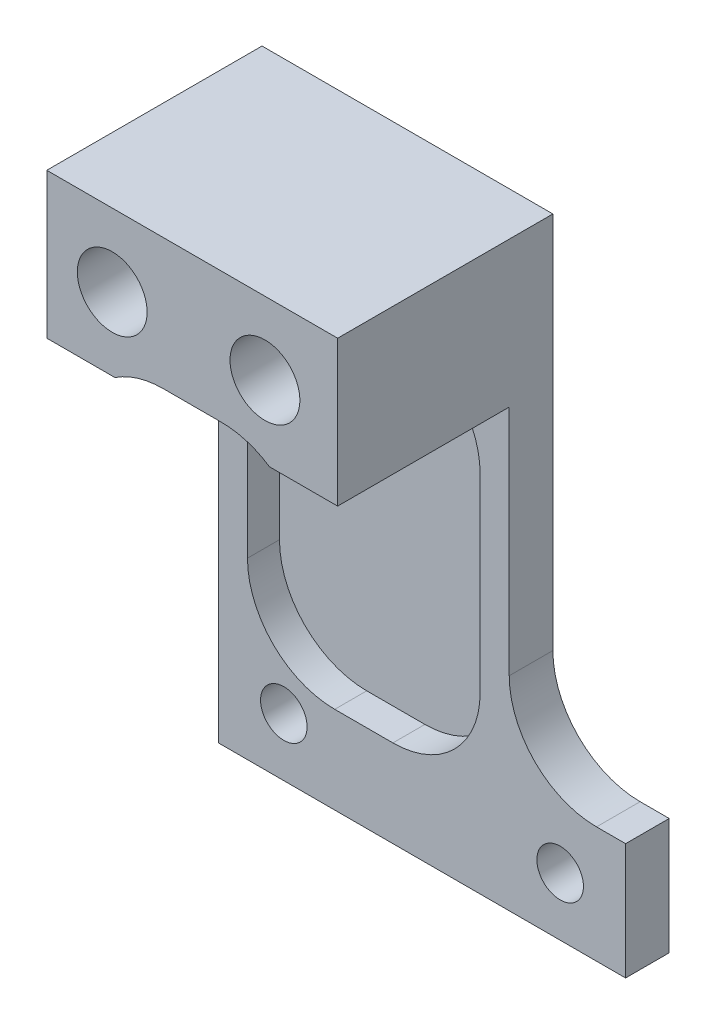
SolidWorks part; units mm, degrees
material "6061-T6 (SS)"
ref_plane "Front Plane" through (0, 0, 0) normal (0, 0, 1) x (1, 0, 0)
ref_plane "Top Plane" through (0, 0, 0) normal (0, 1, 0) x (1, 0, 0)
ref_plane "Right Plane" through (0, 0, 0) normal (1, 0, 0) x (0, 0, -1)
sketch "Sketch1" plane through (0, 0, 0) normal (0, 0, 1) x (1, 0, 0)
  line L0 (-4.75, -8) -> (4.75, -8) construction
  line L1 (7, -10) -> (-7, -10)
  line L2 (7, -10) -> (7, 10)
  line L3 (7, 10) -> (-7, 10)
  line L4 (-7, -10) -> (-7, 10)
  line L5 (7, -10) -> (-7, 10) construction
  line L6 (7, 10) -> (-7, -10) construction
  line L7 (0, 10) -> (0, -8) construction
  line L9 (-4.75, 10) -> (4.75, 10)
  line L10 (-4.75, 10) -> (-4.75, 7.5) construction
  line L11 (-4.75, 7.5) -> (4.75, 7.5) construction
  line L12 (4.75, 10) -> (4.75, 7.5) construction
  point P0 (0, 0)
  point P10 (0, -8)
  dimension "D1" = 14
  dimension "D2" = 20
  dimension "D3" = 2
  dimension "D4" = 9.5
  dimension "D5" = 2.5
extrude "Boss-Extrude1" add sketch "Sketch1" along normal blind 1.5 contours L4 L1 L2 L3 region at (0, 0, 0)
sketch "Sketch2" plane through (0, 0, 1.5) normal (0, 0, 1) x (1, 0, 0)
  line L0 (-7, -10) -> (-7, 10) construction
  line L1 (7, 10) -> (-7, 10)
  line L2 (7, 10) -> (7, 5)
  line L3 (7, 5) -> (-7, 5)
  line L4 (-7, 10) -> (-7, 5)
  dimension "D1" = 5
extrude "Boss-Extrude2" add sketch "Sketch2" along normal blind 5.9
hole_wizard "M2 Tapped Hole1" positions "3DSketch2" profile "Sketch5" tap size "M2" standard "ISO"
sketch3d "3DSketch2"
  point P8 (-4.75, -8, 0)
  point P10 (4.75, -8, 0)
sketch "Sketch5" plane through (-4.75, -8, 0) normal (1, 0, 0) x (0, 1, 0)
  line L0 (0, 0) -> (0, 6.4807)
  line L1 (0, 6.4807) -> (0.8, 6)
  line L2 (0.8, 6) -> (0.8, 0)
  line L5 (0.8, 0) -> (0, 0)
  line L10 (0, 6.4807) -> (-0.8, 6) construction
  line L11 (0, -6.35) -> (0, 107.95) construction
  dimension "Tap Drill Dia." = 1.6
  dimension "Tap Drill Depth" = 6
  dimension "Drill Angle" = 118
sketch "Sketch11" plane through (0, 0, 7.4) normal (0, 0, 1) x (1, 0, 0)
  line L0 (7, 10) -> (-7, 10) construction
  line L1 (7, -6) -> (6, -6)
  line L2 (7, -6) -> (7, 10)
  line L3 (7, 10) -> (3, 10)
  line L4 (3, -3) -> (3, 10)
  line L5 (7, 5) -> (7, 10) construction
  line L6 (7, -10) -> (-7, -10) construction
  arc A0 (6, -6) -> (3, -3) centre (6, -3) cw
  dimension "D3" = 3
  dimension "D1" = 4
  dimension "D2" = 4
extrude "Cut-Extrude6" cut sketch "Sketch11" against normal through all
sketch "Sketch12" plane through (0, 0, 0) normal (0, 0, -1) x (-1, 0, 0)
  line L0 (4.75, 7.5) -> (-0.5, 7.5) construction
  line L1 (-3, 10) -> (-3, -3) construction
  point P0 (4.75, 7.5)
  dimension "D1" = 2.5
hole_wizard "CBORE for M2 Hex Socket Head Cap Screw1" positions "3DSketch3" profile "Sketch13" counterbore size "M2" standard "ISO"
sketch3d "3DSketch3"
  point P0 (-4.75, 7.5, 0)
  point P3 (0.5, 7.5, 0)
sketch "Sketch13" plane through (-4.75, 7.5, 0) normal (1, 0, 0) x (0, 1, 0)
  line L0 (0, 0) -> (0, 8.221)
  line L1 (0, 8.221) -> (1.2, 7.5)
  line L2 (1.2, 7.5) -> (1.2, 2.4)
  line L3 (1.2, 2.4) -> (2.2, 2.4)
  line L4 (2.2, 2.4) -> (2.2, 0)
  line L5 (2.2, 0) -> (0, 0)
  line L10 (0, 8.221) -> (-1.2, 7.5) construction
  line L11 (0, -6.35) -> (0, 107.95) construction
  dimension "Hole Dia." = 2.4
  dimension "Hole Depth" = 7.5
  dimension "C'Bore Dia." = 4.4
  dimension "C'Bore Depth" = 2.4
  dimension "Drill Angle" = 118
sketch "Sketch14" plane through (0, 0, 7.4) normal (0, 0, 1) x (1, 0, 0)
  line L0 (-7, -10) -> (-7, 5) construction
  line L1 (-3, 5.5) -> (-1, 5.5)
  line L2 (-6, 2.5) -> (-6, -4)
  line L3 (-3, -7) -> (-1, -7)
  line L4 (2, 2.5) -> (2, -4)
  line L5 (3, 5) -> (3, -3) construction
  line L7 (-7, 5) -> (3, 5) construction
  line L8 (7, -10) -> (-7, -10) construction
  arc A0 (-3, 5.5) -> (-6, 2.5) centre (-3, 2.5) ccw
  arc A1 (-1, 5.5) -> (2, 2.5) centre (-1, 2.5) cw
  arc A2 (-6, -4) -> (-3, -7) centre (-3, -4) ccw
  arc A3 (-1, -7) -> (2, -4) centre (-1, -4) ccw
  dimension "D5" = 3
  dimension "D1" = 1
  dimension "D2" = 1
  dimension "D3" = 0.5
  dimension "D4" = 3
extrude "Cut-Extrude7" cut sketch "Sketch14" against normal blind 7
equation "\"D2@Sketch14\"=\"D1@Sketch14\""
